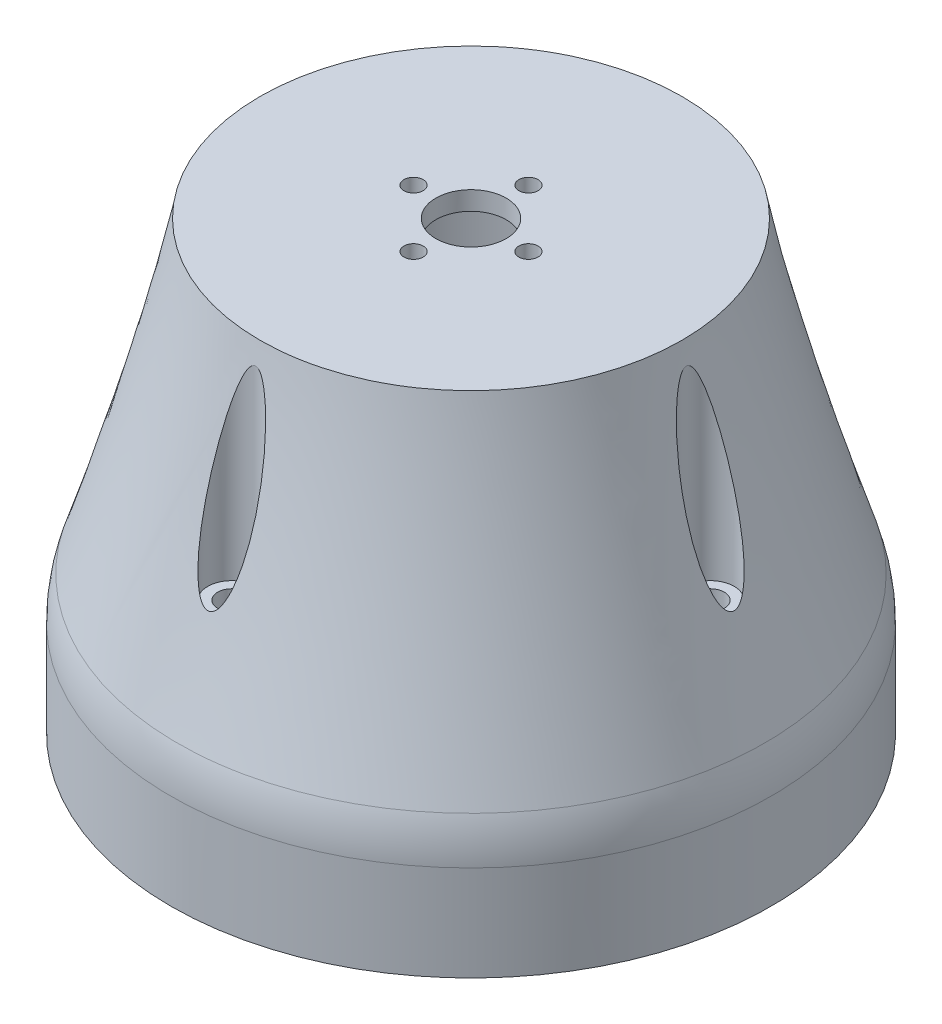
SolidWorks part; units mm, degrees
ref_plane "Front Plane" through (0, 0, 0) normal (0, 0, 1) x (1, 0, 0)
ref_plane "Top Plane" through (0, 0, 0) normal (0, 1, 0) x (1, 0, 0)
ref_plane "Right Plane" through (0, 0, 0) normal (1, 0, 0) x (0, 0, -1)
sketch "Sketch3" plane through (0, 0, 0) normal (0, 1, 0) x (1, 0, 0)
  circle A0 centre (0, 0) radius 64
  dimension "D1" = 128
extrude "Boss-Extrude1" add sketch "Sketch3" along normal blind 15
ref_plane "Plane1" through (0, 85, 0) normal (0, 1, 0) x (1, 0, 0)
sketch "Sketch4" plane through (0, 85, 0) normal (0, 1, 0) x (1, 0, 0)
  circle A0 centre (0, 0) radius 45
  dimension "D1" = 90
sketch "Sketch5" plane through (0, 15, 0) normal (0, 1, 0) x (1, 0, 0)
  circle A1 centre (0, 0) radius 64
  circle A2 centre (0, 0) radius 64
  dimension "D1" = 0
loft "Loft1" add profiles "Sketch5", "Sketch4" connector at (-2.5729, 15, 63.9483) connector at (15.8799, 85, 42.105)
fillet "Fillet1" radius 30 1 edges at (0, 15, 64) type face fillet first side face at (0, 15, 64) second side face at (0, 15, 64)
sketch "Sketch6" plane through (0, 85, 0) normal (0, 1, 0) x (1, 0, 0)
  circle A0 centre (0, 0) radius 51 construction
  circle A1 centre (0, 51) radius 3
  circle A2 centre (51, 0) radius 3
  circle A3 centre (0, -51) radius 3
  circle A4 centre (-51, 0) radius 3
  point P14 (0, 0)
  dimension "D1" = 102
  dimension "D2" = 6
  dimension "D3" = 4
extrude "Cut-Extrude1" cut sketch "Sketch6" against normal blind 85
sketch "Sketch8" plane through (0, 85, 0) normal (0, 1, 0) x (1, 0, 0)
  circle A0 centre (-51, 0) radius 5.11
  circle A1 centre (0, 51) radius 5.11
  circle A2 centre (51, 0) radius 5.11
  circle A3 centre (0, -51) radius 5.11
  point P12 (0, 0)
  dimension "D1" = 10.22
  dimension "D2" = 4
extrude "Cut-Extrude3" cut sketch "Sketch8" against normal blind 45
sketch "Sketch9" plane through (0, 0, 0) normal (0, -1, 0) x (1, 0, 0)
  arc A0 (-16.4684, 53.5238) -> (-53.5238, 16.4684) centre (0, 0) ccw
  arc A1 (-7.1314, 48.6777) -> (7.1314, 48.6777) centre (0, 51) ccw
  arc A5 (-7.1314, 48.6777) -> (-16.4684, 53.5238) centre (-14.2628, 46.3554) ccw
  arc A6 (16.4684, 53.5238) -> (7.1314, 48.6777) centre (14.2628, 46.3554) ccw
  arc A7 (48.6777, 7.1314) -> (53.5238, 16.4684) centre (46.3554, 14.2628) ccw
  arc A8 (48.6777, 7.1314) -> (48.6777, -7.1314) centre (51, 0) ccw
  arc A9 (53.5238, -16.4684) -> (48.6777, -7.1314) centre (46.3554, -14.2628) ccw
  arc A10 (7.1314, -48.6777) -> (16.4684, -53.5238) centre (14.2628, -46.3554) ccw
  arc A11 (7.1314, -48.6777) -> (-7.1314, -48.6777) centre (0, -51) ccw
  arc A12 (-16.4684, -53.5238) -> (-7.1314, -48.6777) centre (-14.2628, -46.3554) ccw
  arc A13 (-48.6777, -7.1314) -> (-53.5238, -16.4684) centre (-46.3554, -14.2628) ccw
  arc A14 (-48.6777, -7.1314) -> (-48.6777, 7.1314) centre (-51, 0) ccw
  arc A15 (-53.5238, 16.4684) -> (-48.6777, 7.1314) centre (-46.3554, 14.2628) ccw
  arc A16 (53.5238, 16.4684) -> (16.4684, 53.5238) centre (0, 0) ccw
  arc A17 (16.4684, -53.5238) -> (53.5238, -16.4684) centre (0, 0) ccw
  arc A18 (-53.5238, -16.4684) -> (-16.4684, -53.5238) centre (0, 0) ccw
  point P15 (0, 0)
  point P35 (0, 0)
  dimension "D1" = 112
  dimension "D2" = 15
  dimension "D3" = 4
  dimension "D4" = 15
  dimension "D5" = 15
extrude "Cut-Extrude4" cut sketch "Sketch9" against normal blind 12
sketch "Sketch17" plane through (0, 12, 0) normal (0, -1, 0) x (1, 0, 0)
  circle A0 centre (0, 0) radius 26
  dimension "D1" = 52
extrude "Cut-Extrude10" cut sketch "Sketch17" against normal blind 69
sketch "Sketch19" plane through (0, 0, 0) normal (0, -1, 0) x (1, 0, 0)
  arc A0 (16.4684, -53.5238) -> (53.5238, -16.4684) centre (0, 0) ccw construction
  circle A1 centre (0, 0) radius 64
  circle A2 centre (0, 0) radius 64
  arc A3 (53.5238, -16.4684) -> (48.6777, -7.1314) centre (46.3554, -14.2628) ccw construction
  arc A4 (48.6777, 7.1314) -> (48.6777, -7.1314) centre (51, 0) ccw construction
  arc A5 (48.6777, 7.1314) -> (53.5238, 16.4684) centre (46.3554, 14.2628) ccw construction
  arc A6 (53.5238, 16.4684) -> (16.4684, 53.5238) centre (0, 0) ccw construction
  arc A7 (-7.1314, 48.6777) -> (7.1314, 48.6777) centre (0, 51) ccw construction
  arc A8 (-7.1314, 48.6777) -> (-16.4684, 53.5238) centre (-14.2628, 46.3554) ccw construction
  arc A9 (16.4684, -53.5238) -> (53.5238, -16.4684) centre (0, 0) ccw
  arc A10 (53.5238, -16.4684) -> (48.6777, -7.1314) centre (46.3554, -14.2628) ccw
  arc A11 (48.6777, 7.1314) -> (48.6777, -7.1314) centre (51, 0) ccw
  arc A12 (48.6777, 7.1314) -> (53.5238, 16.4684) centre (46.3554, 14.2628) ccw
  arc A13 (53.5238, 16.4684) -> (16.4684, 53.5238) centre (0, 0) ccw
  arc A14 (-7.1314, 48.6777) -> (7.1314, 48.6777) centre (0, 51) ccw
  arc A15 (-7.1314, 48.6777) -> (-16.4684, 53.5238) centre (-14.2628, 46.3554) ccw
  arc A18 (16.4684, 53.5238) -> (7.1314, 48.6777) centre (14.2628, 46.3554) ccw
  arc A19 (-7.1314, 48.6777) -> (7.1314, 48.6777) centre (0, 51) ccw
  arc A20 (-7.1314, 48.6777) -> (-16.4684, 53.5238) centre (-14.2628, 46.3554) ccw
  arc A21 (-16.4684, 53.5238) -> (-53.5238, 16.4684) centre (0, 0) ccw
  arc A22 (-53.5238, 16.4684) -> (-48.6777, 7.1314) centre (-46.3554, 14.2628) ccw
  arc A23 (-48.6777, -7.1314) -> (-48.6777, 7.1314) centre (-51, 0) ccw
  arc A24 (-48.6777, -7.1314) -> (-53.5238, -16.4684) centre (-46.3554, -14.2628) ccw
  arc A25 (-53.5238, -16.4684) -> (-16.4684, -53.5238) centre (0, 0) ccw
  arc A26 (-16.4684, -53.5238) -> (-7.1314, -48.6777) centre (-14.2628, -46.3554) ccw
  arc A27 (7.1314, -48.6777) -> (-7.1314, -48.6777) centre (0, -51) ccw
  arc A28 (7.1314, -48.6777) -> (16.4684, -53.5238) centre (14.2628, -46.3554) ccw
  arc A29 (16.4684, -53.5238) -> (53.5238, -16.4684) centre (0, 0) ccw
  arc A30 (53.5238, -16.4684) -> (48.6777, -7.1314) centre (46.3554, -14.2628) ccw
  arc A31 (48.6777, 7.1314) -> (48.6777, -7.1314) centre (51, 0) ccw
  arc A32 (48.6777, 7.1314) -> (53.5238, 16.4684) centre (46.3554, 14.2628) ccw
  arc A33 (53.5238, 16.4684) -> (16.4684, 53.5238) centre (0, 0) ccw
  arc A34 (16.4684, 53.5238) -> (7.1314, 48.6777) centre (14.2628, 46.3554) ccw
  arc A35 (-7.1314, 48.6777) -> (7.1314, 48.6777) centre (0, 51) ccw
  arc A36 (-7.1314, 48.6777) -> (-16.4684, 53.5238) centre (-14.2628, 46.3554) ccw
  arc A37 (-16.4684, 53.5238) -> (-53.5238, 16.4684) centre (0, 0) ccw
  arc A38 (-53.5238, 16.4684) -> (-48.6777, 7.1314) centre (-46.3554, 14.2628) ccw
  arc A39 (-48.6777, -7.1314) -> (-48.6777, 7.1314) centre (-51, 0) ccw
  arc A40 (-48.6777, -7.1314) -> (-53.5238, -16.4684) centre (-46.3554, -14.2628) ccw
  arc A41 (-53.5238, -16.4684) -> (-16.4684, -53.5238) centre (0, 0) ccw
  arc A42 (-16.4684, -53.5238) -> (-7.1314, -48.6777) centre (-14.2628, -46.3554) ccw
  arc A43 (7.1314, -48.6777) -> (-7.1314, -48.6777) centre (0, -51) ccw
  arc A44 (7.1314, -48.6777) -> (16.4684, -53.5238) centre (14.2628, -46.3554) ccw
  arc A45 (16.4684, -53.5238) -> (53.5238, -16.4684) centre (0, 0) ccw
  arc A46 (53.5238, -16.4684) -> (48.6777, -7.1314) centre (46.3554, -14.2628) ccw
  arc A47 (48.6777, 7.1314) -> (48.6777, -7.1314) centre (51, 0) ccw
  arc A48 (48.6777, 7.1314) -> (53.5238, 16.4684) centre (46.3554, 14.2628) ccw
  arc A49 (53.5238, 16.4684) -> (16.4684, 53.5238) centre (0, 0) ccw
  circle M19 centre (0, -51) radius 3
  circle M20 centre (51, 0) radius 3
  circle M21 centre (0, 51) radius 3
  circle M22 centre (-51, 0) radius 3
  circle M23 centre (0, 0) radius 64
  arc M24 (-7.1314, 48.6777) -> (7.1314, 48.6777) centre (0, 51) ccw
  arc M25 (7.1314, 48.6777) -> (16.4684, 53.5238) centre (14.2628, 46.3554) cw
  arc M26 (16.4684, 53.5238) -> (53.5238, 16.4684) centre (0, 0) cw
  arc M27 (53.5238, 16.4684) -> (48.6777, 7.1314) centre (46.3554, 14.2628) cw
  arc M28 (48.6777, 7.1314) -> (48.6777, -7.1314) centre (51, 0) ccw
  arc M29 (48.6777, -7.1314) -> (53.5238, -16.4684) centre (46.3554, -14.2628) cw
  arc M30 (53.5238, -16.4684) -> (16.4684, -53.5238) centre (0, 0) cw
  arc M31 (16.4684, -53.5238) -> (7.1314, -48.6777) centre (14.2628, -46.3554) cw
  arc M32 (7.1314, -48.6777) -> (-7.1314, -48.6777) centre (0, -51) ccw
  arc M33 (-7.1314, -48.6777) -> (-16.4684, -53.5238) centre (-14.2628, -46.3554) cw
  arc M34 (-16.4684, -53.5238) -> (-53.5238, -16.4684) centre (0, 0) cw
  arc M35 (-53.5238, -16.4684) -> (-48.6777, -7.1314) centre (-46.3554, -14.2628) cw
  arc M36 (-48.6777, -7.1314) -> (-48.6777, 7.1314) centre (-51, 0) ccw
  arc M37 (-48.6777, 7.1314) -> (-53.5238, 16.4684) centre (-46.3554, 14.2628) cw
  arc M38 (-53.5238, 16.4684) -> (-16.4684, 53.5238) centre (0, 0) cw
  arc M39 (-16.4684, 53.5238) -> (-7.1314, 48.6777) centre (-14.2628, 46.3554) cw
  dimension "D1" = 0
  dimension "D2" = 0
extrude "Boss-Extrude3" add sketch "Sketch19" along normal blind 10 contours M23 M20 M22 M39 M24 M25 M26 M27 M28 M29 M30 M31 M32 M33 M34 M35 M36 M37 M38 M21 M19 region at (-62.1898, 0, 0)
sketch "Sketch20" plane through (0, 85, 0) normal (0, 1, 0) x (1, 0, 0)
  circle A0 centre (0, 0) radius 12.25 construction
  circle A1 centre (0, 0) radius 7.5
  circle A2 centre (0, 12.25) radius 2.05
  circle A3 centre (12.25, 0) radius 2.05
  circle A4 centre (0, -12.25) radius 2.05
  circle A5 centre (-12.25, 0) radius 2.05
  point P15 (0, 0)
  dimension "D1" = 24.5
  dimension "D2" = 15
  dimension "D3" = 4.1
  dimension "D4" = 4
extrude "Cut-Extrude12" cut sketch "Sketch20" against normal blind 10
